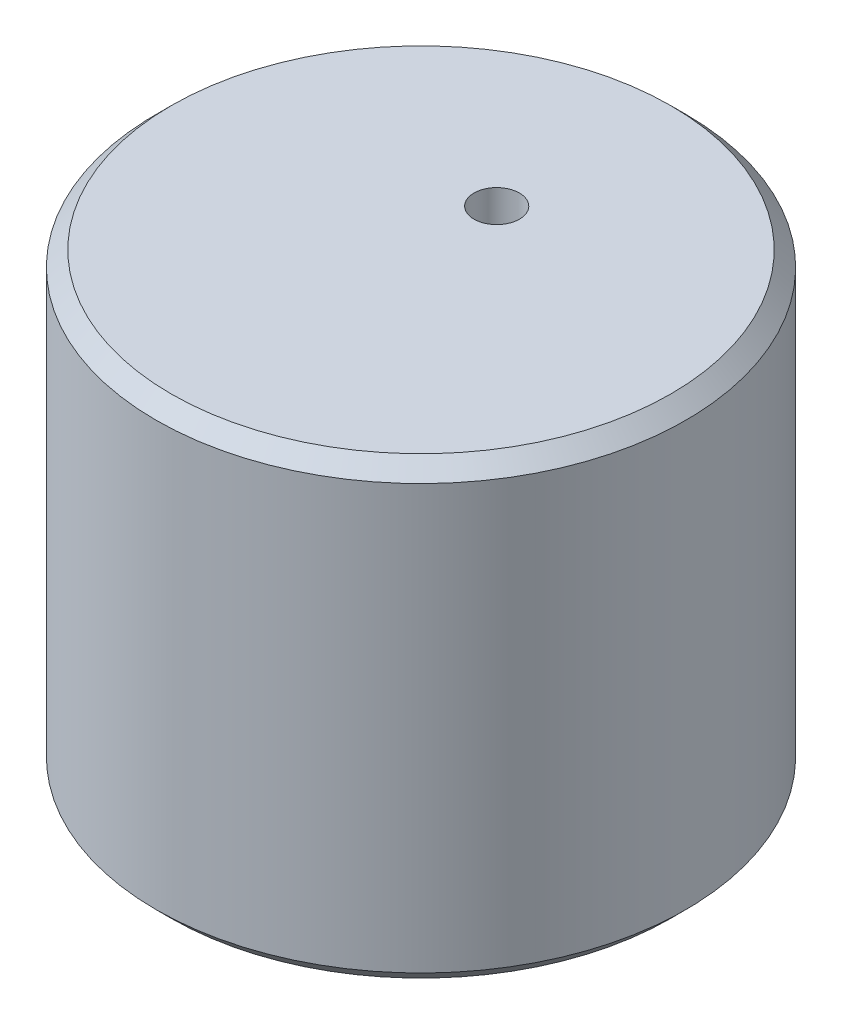
SolidWorks part; units mm, degrees
ref_plane "Front Plane" through (0, 0, 0) normal (0, 0, 1) x (1, 0, 0)
ref_plane "Top Plane" through (0, 0, 0) normal (0, 1, 0) x (1, 0, 0)
ref_plane "Right Plane" through (0, 0, 0) normal (1, 0, 0) x (0, 0, -1)
sketch "Sketch1" plane through (0, 0, 0) normal (0, 1, 0) x (1, 0, 0)
  circle A0 centre (0, 0) radius 17.5
  dimension "D1" = 35
extrude "Boss-Extrude1" add sketch "Sketch1" along normal blind 30
sketch "Sketch2" plane through (0, 0, 0) normal (0, -1, 0) x (1, 0, 0)
  line L0 (0, -17.5) -> (0, 17.5) construction
  line L1 (-17.5, 0) -> (17.5, 0) construction
  line L2 (-1.5, 15) -> (1.5, 15)
  line L3 (-15, 1.5) -> (-15, -1.5)
  line L4 (15, 1.5) -> (15, -1.5)
  line L5 (-1.5, -15) -> (1.5, -15)
  line L6 (-15, 1.5) -> (-1.5, 1.5)
  line L7 (-1.5, 1.5) -> (-1.5, 15)
  line L8 (1.5, 15) -> (1.5, 1.5)
  line L9 (1.5, 1.5) -> (15, 1.5)
  line L10 (15, -1.5) -> (1.5, -1.5)
  line L11 (1.5, -1.5) -> (1.5, -15)
  line L12 (-1.5, -15) -> (-1.5, -1.5)
  line L13 (-1.5, -1.5) -> (-15, -1.5)
  circle A0 centre (0, 0) radius 17.5 construction
  point P10 (0, 15)
  point P13 (-15, 0)
  point P16 (15, 0)
  point P19 (0, -15)
  dimension "D1" = 30
  dimension "D2" = 3
extrude "Boss-Extrude2" add sketch "Sketch2" along normal blind 1
chamfer "Chamfer1" distance 1 angle 45 2 edges at (0, 30, 17.5) (0, 0, 17.5)
sketch "Sketch5" plane through (0, 30, 0) normal (0, 1, 0) x (1, 0, 0)
  line L0 (0, 0) -> (0, 16.5) construction
  circle A0 centre (0, 0) radius 16.5 construction
  circle A1 centre (0, 5) radius 1.5
  point P8 (0, 0)
  point P9 (0, 0)
  point P10 (0, 10.5)
  point P11 (0, 0)
  dimension "D1" = 3
  dimension "D2" = 11.5
extrude "Cut-Extrude1" cut sketch "Sketch5" against normal blind 10
